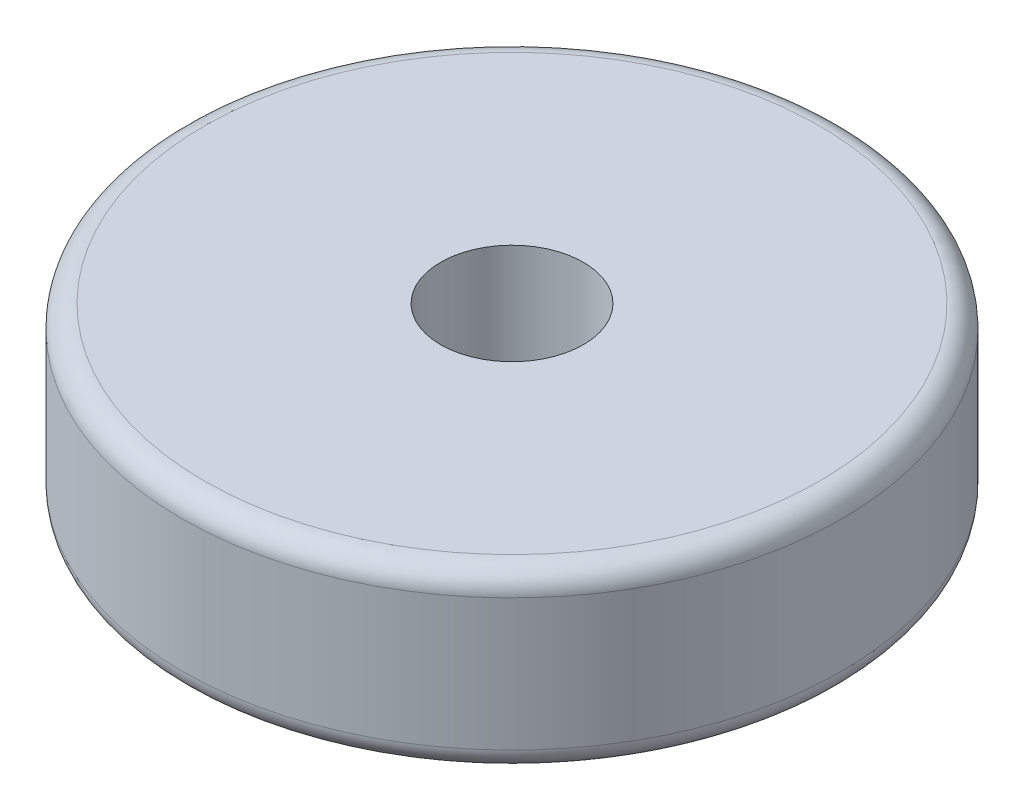
SolidWorks part; units mm, degrees
material "ABS"
ref_plane "Front Plane" through (0, 0, 0) normal (0, 0, 1) x (1, 0, 0)
ref_plane "Top Plane" through (0, 0, 0) normal (0, 1, 0) x (1, 0, 0)
ref_plane "Right Plane" through (0, 0, 0) normal (1, 0, 0) x (0, 0, -1)
sketch "Sketch1" plane through (0, 0, 0) normal (0, 1, 0) x (1, 0, 0)
  circle A0 centre (0, 0) radius 7.5
  dimension "D1" = 15
extrude "Boss-Extrude1" add sketch "Sketch1" along normal blind 4
sketch "Sketch2" plane through (0, 4, 0) normal (0, 1, 0) x (1, 0, 0)
  circle A0 centre (0, 0) radius 1.625
  dimension "D1" = 3.25
extrude "Cut-Extrude1" cut sketch "Sketch2" against normal blind 4
fillet "Fillet1" radius 0.5 2 edges at (0, 0, 7.5) (0, 4, 7.5)
